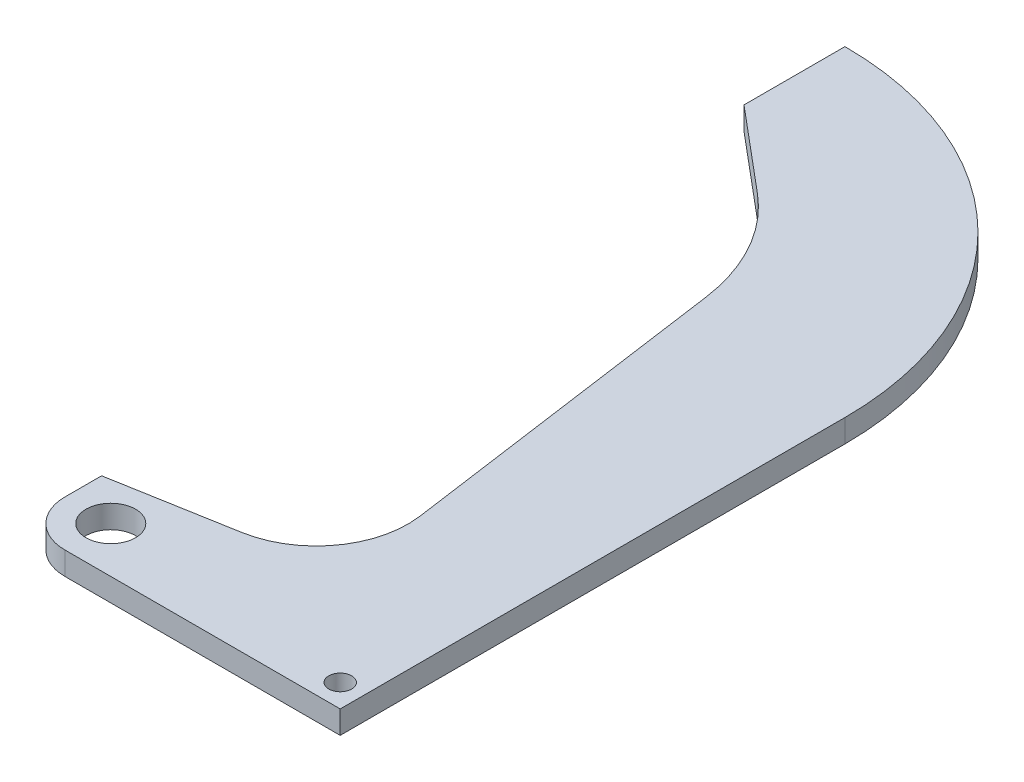
SolidWorks part; units mm, degrees
ref_plane "Front Plane" through (0, 0, 0) normal (0, 0, 1) x (1, 0, 0)
ref_plane "Top Plane" through (0, 0, 0) normal (0, 1, 0) x (1, 0, 0)
ref_plane "Right Plane" through (0, 0, 0) normal (1, 0, 0) x (0, 0, -1)
sketch "Sketch1" plane through (0, 0, 0) normal (0, 1, 0) x (1, 0, 0)
  line L1 (0, 0) -> (44.45, 0)
  line L2 (0, 0) -> (0, 114.3)
  line L4 (44.45, 0) -> (44.45, 69.85)
  circle A0 centre (6.35, 6.35) radius 3.429
  circle A1 centre (41.275, 3.175) radius 1.5875
  arc A2 (44.45, 69.85) -> (0, 114.3) centre (0, 69.85) ccw
  dimension "D3" = 6.858
  dimension "D6" = 3.175
  dimension "D1" = 44.45
  dimension "D4" = 6.35
  dimension "D5" = 6.35
  dimension "D7" = 3.175
  dimension "D8" = 3.175
  dimension "D2" = 114.3
extrude "Boss-Extrude1" add sketch "Sketch1" along normal blind 3.175
sketch "Sketch2" plane through (0, 3.175, 0) normal (0, 1, 0) x (1, 0, 0)
  line L1 (0, 114.3) -> (0, 0) construction
  line L2 (16.4996, 14.3393) -> (0, 11.43)
  line L3 (0, 11.43) -> (0, 100.33)
  line L4 (26.871, 28.6113) -> (20.4054, 74.6866)
  line L5 (11.5786, 90.6144) -> (0, 100.33)
  arc A0 (20.4054, 74.6866) -> (11.5786, 90.6144) centre (-4.7482, 71.1568) ccw
  arc A1 (26.871, 28.6113) -> (16.4996, 14.3393) centre (14.2943, 26.8464) cw
  point P11 (19.05, 84.3452)
  point P14 (28.575, 16.4685)
  dimension "D7" = 25.4
  dimension "D8" = 12.7
  dimension "D1" = 88.9
  dimension "D2" = 11.43
  dimension "D3" = 50
  dimension "D4" = 80
  dimension "D5" = 19.05
  dimension "D6" = 28.575
extrude "Cut-Extrude1" cut sketch "Sketch2" against normal through all
fillet "Fillet1" radius 6.35 1 edges at (0, 1.5875, 0)
equation "\"tightTol\" = 0.005in"
equation "\"normTol\"= 0.01in"
equation "\"looseTol\"= 0.02in"
equation "\"D3@Sketch1\"=\"looseTol\"+0.25"
